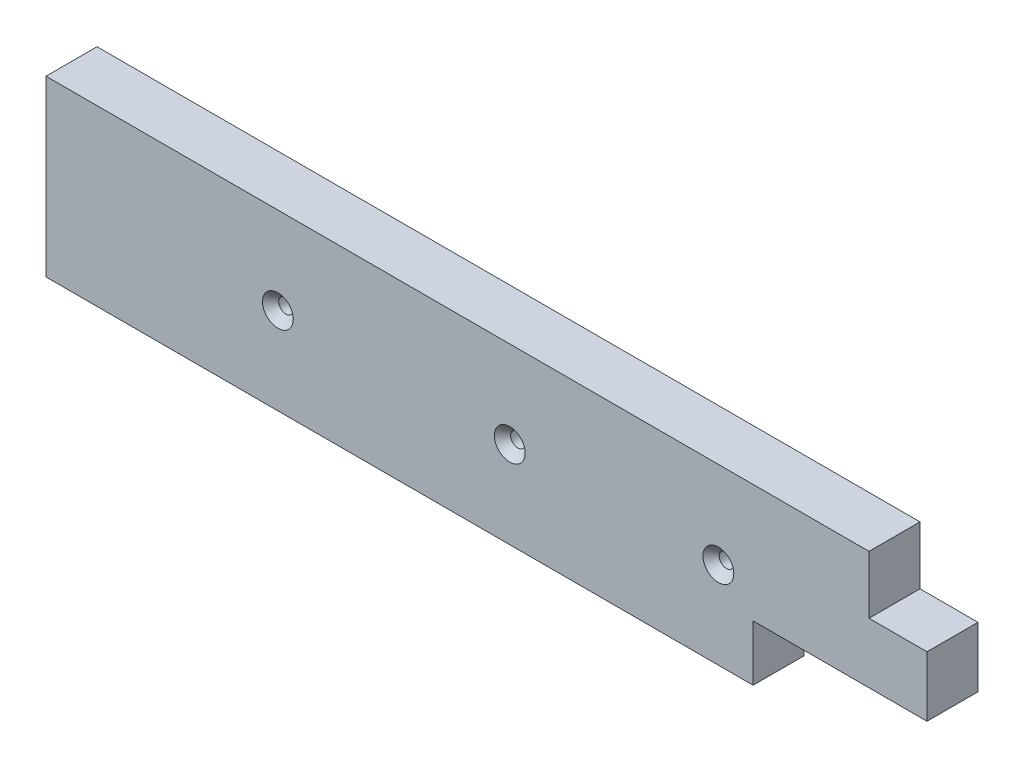
SolidWorks part; units mm, degrees
ref_plane "Front Plane" through (0, 0, 0) normal (0, 0, 1) x (1, 0, 0)
ref_plane "Top Plane" through (0, 0, 0) normal (0, 1, 0) x (1, 0, 0)
ref_plane "Right Plane" through (0, 0, 0) normal (1, 0, 0) x (0, 0, -1)
sketch "Sketch1" plane through (0, 0, 0) normal (0, 1, 0) x (1, 0, 0)
  line L1 (-193.0064, -11.176) -> (193.0064, -11.176)
  line L2 (-193.0064, -11.176) -> (-193.0064, 11.176)
  line L3 (-193.0064, 11.176) -> (193.0064, 11.176)
  line L4 (193.0064, -11.176) -> (193.0064, 11.176)
  line L5 (-193.0064, -11.176) -> (193.0064, 11.176) construction
  line L6 (-193.0064, 11.176) -> (193.0064, -11.176) construction
  point P0 (0, 0)
extrude "Boss-Extrude1" add sketch "Sketch1" along normal mid plane 76.2 contours L1 L4 L3 L2
sketch "Sketch3" plane through (0, 0, 11.176) normal (0, 0, 1) x (1, 0, 0)
  line L1 (167.6064, 12.7) -> (193.0064, 12.7)
  line L2 (193.0064, 38.1) -> (193.0064, 12.7)
  line L3 (167.6064, 12.7) -> (167.6064, 38.1)
  line L4 (167.6064, 38.1) -> (193.0064, 38.1)
  line L5 (116.8199, -13.6854) -> (193.0064, -13.6854)
  line L6 (116.8199, -13.6854) -> (116.8199, -38.1)
  line L7 (116.8199, -38.1) -> (193.0064, -38.1)
  line L8 (193.0064, -13.6854) -> (193.0064, -38.1)
hole_wizard "CSK for M6 Hex Socket Countersunk Head Screw6" positions "Sketch21" profile "Sketch20" countersink size "M6" standard "Lanco STD" end condition through all
sketch "Sketch21" plane through (0, 0, 11.176) normal (0, 0, 1) x (1, 0, 0)
  line L0 (-193.0064, 38.1) -> (-193.0064, -38.1) construction
  point P0 (-91.4064, 0)
  point P3 (-193.0064, 0)
  dimension "D1" = 101.6
sketch "Sketch20" plane through (-91.4064, 0, 11.176) normal (1, 0, 0) x (0, -1, 0)
  line L0 (0, 0) -> (0, 22.352)
  line L1 (0, 22.352) -> (3.2, 22.352)
  line L2 (3.2, 22.352) -> (3.2, 3.55)
  line L3 (3.2, 3.55) -> (6.75, 0)
  line L5 (6.75, 0) -> (0, 0)
  line L6 (-3.2, 3.55) -> (-6.75, 0) construction
  line L11 (0, -6.35) -> (0, 107.95) construction
  dimension "Thru Hole Dia." = 6.4
  dimension "Thru Hole Depth" = 22.352
  dimension "Near C'Sink Dia." = 13.5
  dimension "Near C'Sink Angle" = 90
hole_wizard "CSK for M6 Hex Socket Countersunk Head Screw7" positions "Sketch23" profile "Sketch22" countersink size "M6" standard "Lanco STD" end condition through all
sketch "Sketch23" plane through (0, 0, 11.176) normal (0, 0, 1) x (1, 0, 0)
  line L1 (-193.0064, 38.1) -> (-193.0064, -38.1) construction
  point P0 (10.1936, 0)
  point P5 (-193.0064, 0)
  dimension "D1" = 203.2
sketch "Sketch22" plane through (10.1936, 0, 11.176) normal (1, 0, 0) x (0, -1, 0)
  line L0 (0, 0) -> (0, 22.352)
  line L1 (0, 22.352) -> (3.2, 22.352)
  line L2 (3.2, 22.352) -> (3.2, 3.55)
  line L3 (3.2, 3.55) -> (6.75, 0)
  line L5 (6.75, 0) -> (0, 0)
  line L6 (-3.2, 3.55) -> (-6.75, 0) construction
  line L11 (0, -6.35) -> (0, 107.95) construction
  dimension "Thru Hole Dia." = 6.4
  dimension "Thru Hole Depth" = 22.352
  dimension "Near C'Sink Dia." = 13.5
  dimension "Near C'Sink Angle" = 90
hole_wizard "CSK for M6 Hex Socket Countersunk Head Screw8" positions "Sketch25" profile "Sketch24" countersink size "M6" standard "Lanco STD" end condition through all
sketch "Sketch25" plane through (0, 0, 11.176) normal (0, 0, 1) x (1, 0, 0)
  point P0 (101.6, 0)
  dimension "D1" = 101.6
sketch "Sketch24" plane through (101.6, 0, 11.176) normal (1, 0, 0) x (0, -1, 0)
  line L0 (0, 0) -> (0, 22.352)
  line L1 (0, 22.352) -> (3.2, 22.352)
  line L2 (3.2, 22.352) -> (3.2, 3.55)
  line L3 (3.2, 3.55) -> (6.75, 0)
  line L5 (6.75, 0) -> (0, 0)
  line L6 (-3.2, 3.55) -> (-6.75, 0) construction
  line L11 (0, -6.35) -> (0, 107.95) construction
  dimension "Thru Hole Dia." = 6.4
  dimension "Thru Hole Depth" = 22.352
  dimension "Near C'Sink Dia." = 13.5
  dimension "Near C'Sink Angle" = 90
extrude "Cut-Extrude1" cut sketch "Sketch3" against normal through all
